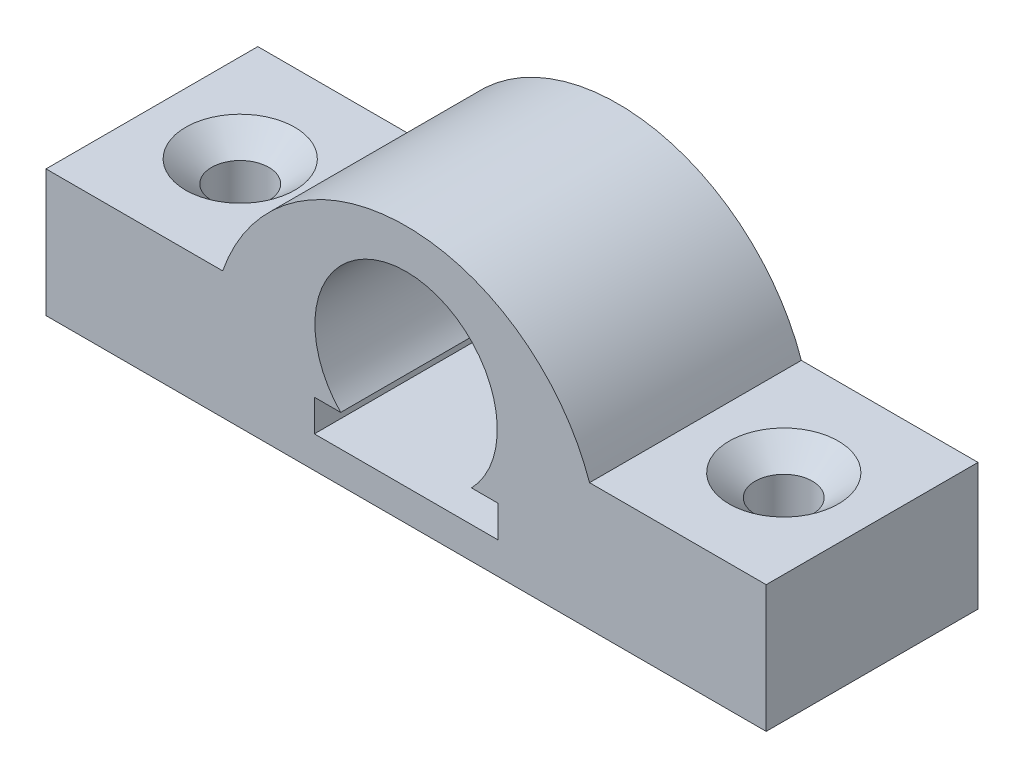
SolidWorks part; units mm, degrees
ref_plane "Front Plane" through (0, 0, 0) normal (0, 0, 1) x (1, 0, 0)
ref_plane "Top Plane" through (0, 0, 0) normal (0, 1, 0) x (1, 0, 0)
ref_plane "Right Plane" through (0, 0, 0) normal (1, 0, 0) x (0, 0, -1)
sketch "Sketch2" plane through (0, 0, 0) normal (0, 1, 0) x (1, 0, 0)
  line L0 (0, 0) -> (85, 0)
  line L1 (85, 0) -> (85, 25)
  line L2 (85, 25) -> (0, 25)
  line L3 (0, 25) -> (0, 0)
  dimension "D1" = 85
  dimension "D2" = 25
extrude "Boss-Extrude1" add sketch "Sketch2" along normal blind 15
sketch "Sketch6" plane through (0, 0, 0) normal (0, 0, 1) x (1, 0, 0)
  line L0 (42.5, 0) -> (42.5, 15) construction
  line L1 (0, 0) -> (85, 0) construction
  line L2 (0, 15) -> (85, 15) construction
  line L3 (42.5, 15) -> (85, 15) construction
  line L4 (42.5, 15) -> (0, 15) construction
  line L5 (42.5, 7.5) -> (42.5, 15) construction
  line L6 (42.5, 7.5) -> (42.5, 15) construction
  line L7 (42.5, 7.5) -> (42.5, 15) construction
  line L8 (20.8494, 15) -> (64.1506, 15)
  arc A0 (20.8494, 15) -> (64.1506, 15) centre (42.5, 7.5) cw
extrude "Boss-Extrude3" add sketch "Sketch6" against normal blind 25
sketch "Sketch7" plane through (0, 0, 0) normal (0, 0, 1) x (1, 0, 0)
  line L0 (42.5, 0) -> (20.8494, 15) construction
  line L1 (0, 0) -> (85, 0) construction
  line L2 (20.8494, 15) -> (64.1506, 15) construction
  line L3 (64.1506, 15) -> (42.5, 0) construction
  line L8 (20.8494, 15) -> (20.8494, 0) construction
  line L9 (64.1506, 15) -> (64.1506, 0) construction
  line L10 (20.8494, 7.5) -> (20.8494, 0) construction
  line L11 (20.8494, 0) -> (64.1506, 0) construction
  line L12 (64.1506, 0) -> (64.1506, 7.5) construction
  line L13 (64.1506, 7.5) -> (20.8494, 7.5) construction
  line L14 (20.8494, 7.5) -> (20.8494, 0) construction
  line L15 (20.8494, 0) -> (64.1506, 0) construction
  line L16 (64.1506, 0) -> (64.1506, 7.5) construction
  line L17 (64.1506, 0) -> (64.1506, 7.5) construction
  line L18 (53.3253, 7.5) -> (53.3253, 3.75)
  line L19 (20.8494, 7.5) -> (20.8494, 3.75) construction
  line L20 (31.6747, 7.5) -> (31.6747, 3.75)
  line L21 (31.6747, 3.75) -> (53.3253, 3.75)
  line L22 (31.6747, 7.5) -> (53.3253, 7.5)
  line L23 (42.5, 3.75) -> (42.5, 15) construction
  line L24 (42.5, 7.5) -> (31.6747, 7.5) construction
  line L25 (42.5, 7.5) -> (31.6747, 7.5) construction
  line L26 (35.9208, 6.4826) -> (36.1689, 6.2967)
  line L27 (13.75, 0) -> (-13.75, 0) construction
  arc A1 (36.1689, 6.2967) -> (35.9208, 6.4826) centre (42.5, 15) ccw
sketch "Sketch10" plane through (0, 15, 0) normal (0, 1, 0) x (1, 0, 0)
  line L0 (0, 12.5) -> (20.8494, 12.5) construction
  line L1 (0, 25) -> (0, 0) construction
  line L2 (20.8494, 25) -> (20.8494, 0) construction
  line L3 (64.1506, 12.5) -> (85, 12.5) construction
  line L4 (64.1506, 25) -> (64.1506, 0) construction
  line L5 (85, 0) -> (85, 25) construction
  circle A0 centre (10.4247, 12.5) radius 5
  circle A1 centre (74.5753, 12.5) radius 5
  point P12 (10.4247, 12.5)
  point P14 (74.5753, 12.5)
hole_wizard "CSK for 1/4 Flat Head Machine Screw (100)1" positions "Sketch10" profile "Sketch11" countersink size "1/4" standard "ANSI Inch" end condition through all
sketch "Sketch11" plane through (74.5753, 15, -12.5) normal (1, 0, 0) x (0, 0, 1)
  line L0 (0, 0) -> (0, 15)
  line L1 (0, 15) -> (3.3782, 15)
  line L2 (3.3782, 15) -> (3.3782, 2.5682)
  line L3 (3.3782, 2.5682) -> (6.4389, 0)
  line L5 (6.4389, 0) -> (0, 0)
  line L6 (-3.3782, 2.5682) -> (-6.4389, 0) construction
  line L11 (0, -6.35) -> (0, 107.95) construction
  dimension "Thru Hole Dia." = 6.7564
  dimension "Thru Hole Depth" = 15
  dimension "Near C'Sink Dia." = 12.8778
  dimension "Near C'Sink Angle" = 100
ref_axis "Axis1" through (42.5, 15, 0) along (0, 0, 1)
extrude "Cut-Extrude1" cut sketch "Sketch7" against normal blind 55 contours L22 A1 | A1 L22 L20 L21 L18 L26 | L22 A1 L26 region at (53.1056, 5.625, 0) region at (42.5, 6.1764, 0) region at (42.5, 15.9315, 0)
